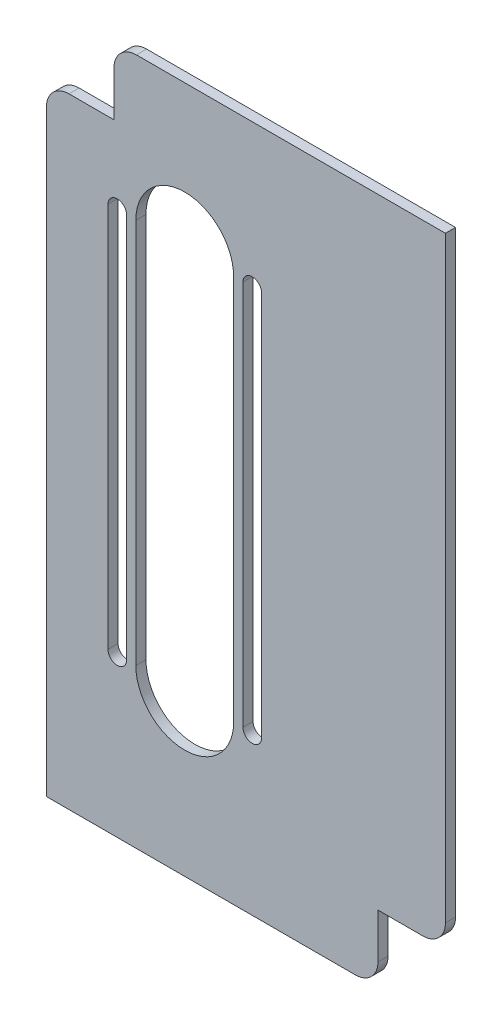
SolidWorks part; units mm, degrees
ref_plane "Front Plane" through (0, 0, 0) normal (0, 0, 1) x (1, 0, 0)
ref_plane "Top Plane" through (0, 0, 0) normal (0, 1, 0) x (1, 0, 0)
ref_plane "Right Plane" through (0, 0, 0) normal (1, 0, 0) x (0, 0, -1)
sketch "Sketch1" plane through (0, 0, 0) normal (0, 0, 1) x (1, 0, 0)
  line L1 (0, 0) -> (118.275, 0)
  line L2 (0, 0) -> (0, 203.74)
  line L3 (0, 203.74) -> (118.275, 203.74)
  line L4 (118.275, 0) -> (118.275, 203.74)
  dimension "D1" = 118.275
  dimension "D2" = 203.74
extrude "Boss-Extrude1" add sketch "Sketch1" along normal blind 3
sketch "Sketch2" plane through (0, 0, 3) normal (0, 0, 1) x (1, 0, 0)
  line L0 (118.275, 203.74) -> (0, 203.74) construction
  line L1 (41, 203.74) -> (41, 0) construction
  line L2 (0, 203.74) -> (0, 0) construction
  line L3 (0, 0) -> (118.275, 0) construction
  line L4 (0, 104.05) -> (118.275, 104.05) construction
  line L5 (118.275, 0) -> (118.275, 203.74) construction
  line L6 (41, 161.1959) -> (41, 46.9041) construction
  line L7 (55.5, 161.1959) -> (55.5, 46.9041)
  line L8 (26.5, 161.1959) -> (26.5, 46.9041)
  line L9 (61, 161.1959) -> (61, 46.9041) construction
  line L10 (63.75, 161.1959) -> (63.75, 46.9041)
  line L11 (58.25, 161.1959) -> (58.25, 46.9041)
  line L12 (21, 161.1959) -> (21, 46.9041) construction
  line L13 (23.75, 161.1959) -> (23.75, 46.9041)
  line L14 (18.25, 161.1959) -> (18.25, 46.9041)
  arc A1 (55.5, 161.1959) -> (26.5, 161.1959) centre (41, 161.1959) ccw
  arc A2 (26.5, 46.9041) -> (55.5, 46.9041) centre (41, 46.9041) ccw
  arc A3 (63.75, 161.1959) -> (58.25, 161.1959) centre (61, 161.1959) ccw
  arc A4 (58.25, 46.9041) -> (63.75, 46.9041) centre (61, 46.9041) ccw
  arc A5 (23.75, 161.1959) -> (18.25, 161.1959) centre (21, 161.1959) ccw
  arc A6 (18.25, 46.9041) -> (23.75, 46.9041) centre (21, 46.9041) ccw
  point P16 (41, 104.05)
  point P21 (61, 104.05)
  point P28 (21, 104.05)
  dimension "D1" = 29
  dimension "D4" = 99.69
  dimension "D5" = 5.5
  dimension "D6" = 5.5
  dimension "D7" = 20
  dimension "D8" = 20
extrude "Cut-Extrude1" cut sketch "Sketch2" against normal blind 3
sketch "Sketch3" plane through (0, 0, 3) normal (0, 0, 1) x (1, 0, 0)
  line L1 (0, 203.74) -> (20, 203.74)
  line L2 (0, 203.74) -> (0, 183.74)
  line L3 (0, 183.74) -> (20, 183.74)
  line L4 (20, 203.74) -> (20, 183.74)
  line L5 (118.275, 0) -> (98.275, 0)
  line L6 (118.275, 0) -> (118.275, 20)
  line L7 (118.275, 20) -> (98.275, 20)
  line L8 (98.275, 0) -> (98.275, 20)
  dimension "D1" = 20
  dimension "D2" = 20
  dimension "D3" = 20
  dimension "D4" = 20
extrude "Cut-Extrude2" cut sketch "Sketch3" against normal blind 10
fillet "Fillet1" radius 6.7 4 edges at (98.275, 0, 1.5) (118.275, 20, 1.5) (20, 203.74, 1.5) (0, 183.74, 1.5)
